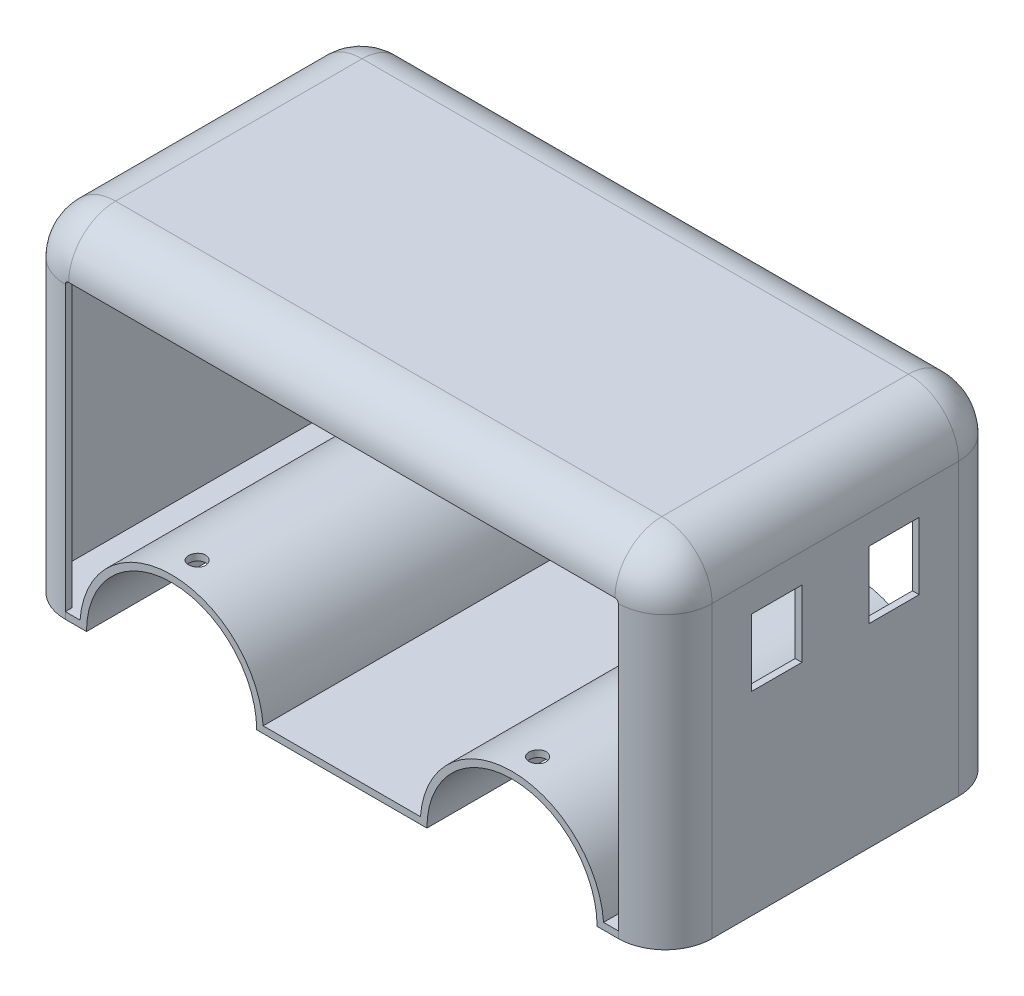
SolidWorks part; units mm, degrees
ref_plane "Front Plane" through (0, 0, 0) normal (0, 0, 1) x (1, 0, 0)
ref_plane "Top Plane" through (0, 0, 0) normal (0, 1, 0) x (1, 0, 0)
ref_plane "Right Plane" through (0, 0, 0) normal (1, 0, 0) x (0, 0, -1)
sketch "Sketch1" plane through (0, 0, 0) normal (0, 0, 1) x (1, 0, 0)
  line L0 (-127, 0) -> (127, 0)
  line L1 (-407.6, 508) -> (407.6, 508)
  line L2 (-482.6, 433) -> (-482.6, 0)
  line L3 (-482.6, 0) -> (-381, 0)
  line L4 (482.6, 433) -> (482.6, 0)
  line L5 (381, 0) -> (482.6, 0)
  arc A0 (-407.6, 508) -> (-482.6, 433) centre (-407.6, 433) ccw
  arc A1 (482.6, 433) -> (407.6, 508) centre (407.6, 433) ccw
  arc A2 (-127, 0) -> (-381, 0) centre (-254, 0) ccw
  arc A3 (381, 0) -> (127, 0) centre (254, 0) ccw
  dimension "D5" = 150
  dimension "D6" = 150
  dimension "D7" = 254
  dimension "D8" = 254
  dimension "D1" = 965.2
  dimension "D2" = 508
  dimension "D3" = 482.6
  dimension "D4" = 508
  dimension "D9" = 508
  dimension "D10" = 254
extrude "Boss-Extrude1" add sketch "Sketch1" along normal mid plane 508
fillet "Fillet1" radius 70 10 edges at (482.6, 216.5, 254) (460.633, 486.033, 254) (-482.6, 216.5, 254) (-460.633, 486.033, 254) (482.6, 216.5, -254) (460.633, 486.033, -254) (-482.6, 216.5, -254) (-460.633, 486.033, -254) (0, 508, 254) (0, 508, -254)
shell "Shell3" thickness 10 removed face at (0, 199.8071, 254) removed face at (0, 199.8071, -254)
ref_plane "Plane1" through (0, -101.6, 0) normal (0, -1, 0) x (-1, 0, 0)
ref_plane "Plane2" through (0, 0, 0) normal (0, -1, 0) x (-1, 0, 0)
ref_plane "Plane3" through (0, 140, 0) normal (0, -1, 0) x (-1, 0, 0)
sketch "Sketch2" plane through (0, 140, 0) normal (0, -1, 0) x (-1, 0, 0)
  line L0 (-127, 254) -> (-381, 254) construction
  line L1 (381, 254) -> (127, 254) construction
  line L2 (127, -254) -> (381, -254) construction
  line L3 (-381, -254) -> (-127, -254) construction
  circle A0 centre (-254, 215.9) radius 12.7
  circle A1 centre (254, 215.9) radius 12.7
  circle A2 centre (254, -215.9) radius 12.7
  circle A3 centre (-254, -215.9) radius 12.7
  dimension "D1" = 25.4
  dimension "D2" = 25.4
  dimension "D3" = 25.4
  dimension "D4" = 25.4
  dimension "D5" = 254
  dimension "D6" = 38.1
  dimension "D7" = 38.1
  dimension "D8" = 254
  dimension "D9" = 38.1
  dimension "D10" = 38.1
  dimension "D11" = 254
  dimension "D12" = 254
extrude "Cut-Extrude1" cut sketch "Sketch2" along normal blind 107 contours A3 | A0 | A1 | A2
sketch "Sketch3" plane through (482.6, 0, 0) normal (1, 0, 0) x (0, 0, -1)
  line L1 (-125, 390) -> (-50, 390)
  line L2 (-125, 390) -> (-125, 290)
  line L3 (-125, 290) -> (-50, 290)
  line L4 (-50, 390) -> (-50, 290)
  line L5 (50, 390) -> (125, 390)
  line L6 (50, 390) -> (50, 290)
  line L7 (50, 290) -> (125, 290)
  line L8 (125, 390) -> (125, 290)
  line L9 (-384.9663, 0) -> (384.9663, 0) construction
  line L10 (-184, 0) -> (184, 0) construction
  point P12 (0, 0)
  dimension "D1" = 100
  dimension "D2" = 75
  dimension "D3" = 75
  dimension "D4" = 100
  dimension "D5" = 290
  dimension "D6" = 290
  dimension "D7" = 50
  dimension "D8" = 50
extrude "Cut-Extrude2" cut sketch "Sketch3" against normal blind 10
ref_axis "Axis1" through (-254, 125.6426, 215.9) along (0, 1, 0)
ref_axis "Axis2" through (254, 99.3051, 215.9) along (0, 1, 0)
ref_axis "Axis3" through (254, 72.2514, -215.9) along (0, 1, 0)
ref_axis "Axis4" through (-254, 125.6426, -215.9) along (0, 1, 0)
